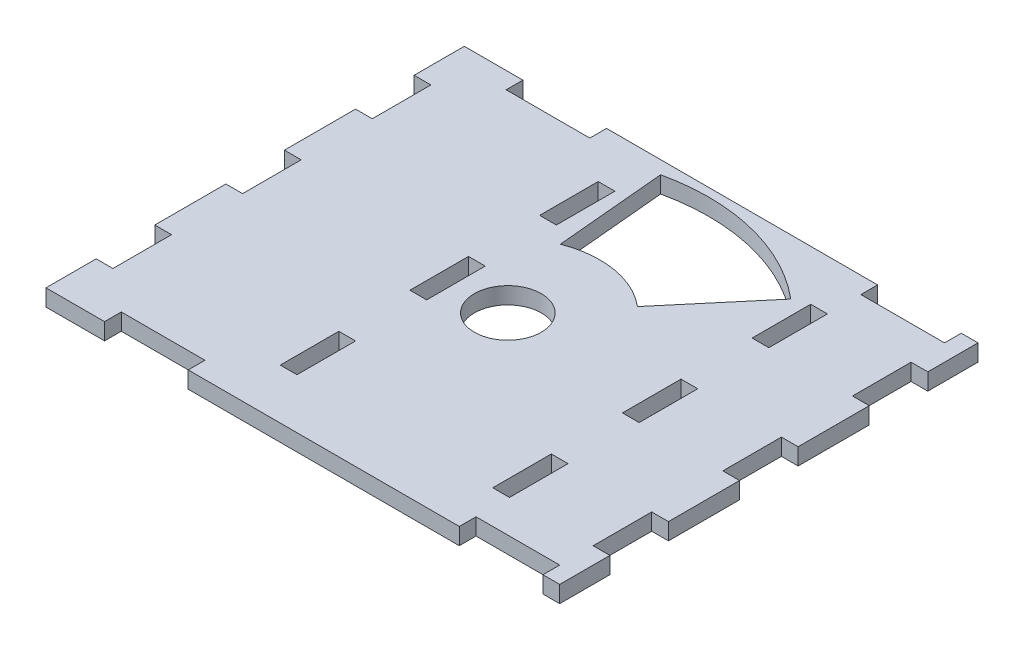
SolidWorks part; units mm, degrees
ref_plane "Front Plane" through (0, 0, 0) normal (0, 0, 1) x (1, 0, 0)
ref_plane "Top Plane" through (0, 0, 0) normal (0, 1, 0) x (1, 0, 0)
ref_plane "Right Plane" through (0, 0, 0) normal (1, 0, 0) x (0, 0, -1)
sketch "Sketch2" plane through (0, 0, 0) normal (0, 1, 0) x (1, 0, 0)
  line L1 (-50, 25) -> (50, 25)
  line L2 (-50, 25) -> (-50, -25)
  line L3 (-50, -25) -> (50, -25)
  line L4 (50, 25) -> (50, -25)
  line L5 (-50, 25) -> (50, -25) construction
  line L6 (-50, -25) -> (50, 25) construction
  circle A0 centre (0, 0) radius 4
  point P0 (0, 0)
  dimension "D3" = 8
  dimension "D1" = 100
  dimension "D2" = 50
extrude "Boss-Extrude1" add sketch "Sketch2" along normal blind 2
sketch "Sketch5" plane through (0, 0, 0) normal (0, -1, 0) x (-1, 0, 0)
  line L0 (-50, 25) -> (50, 25) construction
  line L1 (-17.2, -19) -> (-19.2, -19)
  line L2 (-17.2, -19) -> (-17.2, -12)
  line L3 (-17.2, -12) -> (-19.2, -12)
  line L4 (-19.2, -19) -> (-19.2, -12)
  line L5 (-17.2, -3.5) -> (-19.2, -3.5)
  line L6 (-17.2, -3.5) -> (-17.2, 3.5)
  line L7 (-17.2, 3.5) -> (-19.2, 3.5)
  line L8 (-19.2, -3.5) -> (-19.2, 3.5)
  line L9 (-17.2, 12) -> (-19.2, 12)
  line L10 (-17.2, 12) -> (-17.2, 19)
  line L11 (-17.2, 19) -> (-19.2, 19)
  line L12 (-19.2, 12) -> (-19.2, 19)
  line L13 (8.2, 12) -> (6.2, 12)
  line L14 (8.2, 12) -> (8.2, 19)
  line L15 (8.2, 19) -> (6.2, 19)
  line L16 (6.2, 12) -> (6.2, 19)
  line L17 (8.2, -3.5) -> (6.2, -3.5)
  line L18 (8.2, -3.5) -> (8.2, 3.5)
  line L19 (8.2, 3.5) -> (6.2, 3.5)
  line L20 (6.2, -3.5) -> (6.2, 3.5)
  line L21 (8.2, -19) -> (6.2, -19)
  line L22 (8.2, -19) -> (8.2, -12)
  line L23 (8.2, -12) -> (6.2, -12)
  line L24 (6.2, -19) -> (6.2, -12)
  line L25 (50, -25) -> (-50, -25) construction
  line L26 (-50, 25) -> (50, 25) construction
  line L27 (50, -25) -> (-50, -25) construction
  point P29 (-18.2, -19)
  dimension "D1" = 2
  dimension "D2" = 7
  dimension "D3" = 7
  dimension "D4" = 7
  dimension "D5" = 2
  dimension "D6" = 2
  dimension "D7" = 2
  dimension "D8" = 2
  dimension "D9" = 2
  dimension "D10" = 7
  dimension "D11" = 7
  dimension "D12" = 7
  dimension "D13" = 6
  dimension "D14" = 8.5
  dimension "D15" = 8.5
  dimension "D16" = 6
  dimension "D17" = 6
  dimension "D18" = 8.5
  dimension "D19" = 8.5
  dimension "D20" = 6
  dimension "D21" = 6.2
  dimension "D22" = 0
  dimension "D23" = 17.2
extrude "Cut-Extrude3" cut sketch "Sketch5" against normal blind 2
sketch "Sketch10" plane through (0, 2, 0) normal (0, 1, 0) x (1, 0, 0)
  line L0 (-5.1716, 23.4362) -> (-3.9753, 10.2565)
  line L1 (15.4739, 18.3455) -> (7.0922, 8.4084)
  arc A0 (-3.9753, 10.2565) -> (7.0922, 8.4084) centre (0, 0) cw
  arc A1 (-5.1716, 23.4362) -> (15.4739, 18.3455) centre (0, 0) cw
  point P2 (15.4739, 18.3455)
  dimension "D1" = 24
  dimension "D2" = 11
extrude "Cut-Extrude6" cut sketch "Sketch10" against normal blind 2 contours A1 L0 A0 L1 region at (3.832, 2, -17.0402)
sketch "Sketch11" plane through (0, 2, 0) normal (0, 1, 0) x (1, 0, 0)
  line L0 (-50, -25) -> (50, -25) construction
  line L1 (-18.2, -25) -> (-13.2, -25)
  line L2 (-18.2, -25) -> (-18.2, -23)
  line L3 (-18.2, -23) -> (-13.2, -23)
  line L4 (-13.2, -25) -> (-13.2, -23)
  line L5 (50, 25) -> (-50, 25) construction
  line L6 (29.2, -25) -> (24.2, -25)
  line L7 (29.2, -25) -> (29.2, -23)
  line L8 (29.2, -23) -> (24.2, -23)
  line L9 (24.2, -25) -> (24.2, -23)
  line L10 (29.2, 25) -> (24.2, 25)
  line L11 (29.2, 25) -> (29.2, 23)
  line L12 (29.2, 23) -> (24.2, 23)
  line L13 (24.2, 25) -> (24.2, 23)
  line L15 (-18.2, 25) -> (-13.2, 25)
  line L16 (-18.2, 25) -> (-18.2, 23)
  line L17 (-18.2, 23) -> (-13.2, 23)
  line L18 (-13.2, 25) -> (-13.2, 23)
  dimension "D1" = 2
  dimension "D2" = 2
  dimension "D3" = 2
  dimension "D4" = 2
  dimension "D5" = 5
  dimension "D6" = 5
  dimension "D7" = 5
  dimension "D8" = 5
  dimension "D9" = 5
  dimension "D10" = 5
  dimension "D11" = 5
  dimension "D12" = 5
extrude "Cut-Extrude7" cut sketch "Sketch11" against normal blind 2
sketch "Sketch12" plane through (0, 2, 0) normal (0, 1, 0) x (1, 0, 0)
  line L0 (-50, -25) -> (-18.2, -25) construction
  line L1 (-40.2, -25) -> (-50, -25)
  line L2 (-40.2, -25) -> (-40.2, 25)
  line L3 (-40.2, 25) -> (-50, 25)
  line L4 (-50, -25) -> (-50, 25)
  line L5 (29.2, -25) -> (50, -25) construction
  line L6 (41.2, -25) -> (50, -25)
  line L7 (41.2, -25) -> (41.2, 25)
  line L8 (41.2, 25) -> (50, 25)
  line L9 (50, -25) -> (50, 25)
  line L10 (-18.2, 25) -> (-18.2, 23) construction
  point P16 (-18.2, 24)
  dimension "D1" = 22
  dimension "D2" = 12
extrude "Cut-Extrude8" cut sketch "Sketch12" against normal blind 6
sketch "Sketch13" plane through (0, 2, 0) normal (0, 1, 0) x (1, 0, 0)
  line L1 (-28.2, 19) -> (-30.2, 19)
  line L2 (-28.2, 19) -> (-28.2, 12)
  line L3 (-28.2, 12) -> (-30.2, 12)
  line L4 (-30.2, 19) -> (-30.2, 12)
  line L5 (-28.2, 3.5) -> (-30.2, 3.5)
  line L6 (-28.2, 3.5) -> (-28.2, -3.5)
  line L7 (-28.2, -3.5) -> (-30.2, -3.5)
  line L8 (-30.2, 3.5) -> (-30.2, -3.5)
  line L9 (-28.2, -12) -> (-30.2, -12)
  line L10 (-28.2, -12) -> (-28.2, -19)
  line L11 (-28.2, -19) -> (-30.2, -19)
  line L12 (-30.2, -12) -> (-30.2, -19)
  line L13 (29.2, 19) -> (31.2, 19)
  line L14 (29.2, 19) -> (29.2, 12)
  line L15 (29.2, 12) -> (31.2, 12)
  line L16 (31.2, 19) -> (31.2, 12)
  line L17 (29.2, 3.5) -> (31.2, 3.5)
  line L18 (29.2, 3.5) -> (29.2, -3.5)
  line L19 (29.2, -3.5) -> (31.2, -3.5)
  line L20 (31.2, 3.5) -> (31.2, -3.5)
  line L21 (29.2, -12) -> (31.2, -12)
  line L22 (29.2, -12) -> (29.2, -19)
  line L23 (29.2, -19) -> (31.2, -19)
  line L24 (31.2, -12) -> (31.2, -19)
  line L26 (24.2, 25) -> (-13.2, 25) construction
  line L27 (41.2, 25) -> (29.2, 25) construction
  line L28 (29.2, -25) -> (41.2, -25) construction
  line L29 (-18.2, 25) -> (-40.2, 25) construction
  line L30 (-40.2, -25) -> (-18.2, -25) construction
  line L31 (-40.2, -25) -> (-30.2, -25)
  line L32 (-40.2, -25) -> (-40.2, 25)
  line L33 (-40.2, 25) -> (-30.2, 25)
  line L34 (-30.2, -25) -> (-30.2, 25)
  line L35 (41.2, -25) -> (31.2, -25)
  line L36 (41.2, -25) -> (41.2, 25)
  line L37 (41.2, 25) -> (31.2, 25)
  line L38 (31.2, -25) -> (31.2, 25)
  line L39 (24.2, -25) -> (19.2, -25)
  line L40 (24.2, -25) -> (24.2, -23)
  line L41 (24.2, -23) -> (19.2, -23)
  line L42 (19.2, -25) -> (19.2, -23)
  line L43 (24.2, 23) -> (19.2, 23)
  line L44 (24.2, 23) -> (24.2, 25)
  line L45 (24.2, 25) -> (19.2, 25)
  line L46 (19.2, 23) -> (19.2, 25)
  line L48 (-23.2, 25) -> (-18.2, 25)
  line L49 (-23.2, 25) -> (-23.2, 23)
  line L50 (-23.2, 23) -> (-18.2, 23)
  line L51 (-18.2, 25) -> (-18.2, 23)
  line L52 (-23.2, -25) -> (-18.2, -25)
  line L53 (-23.2, -25) -> (-23.2, -23)
  line L54 (-23.2, -23) -> (-18.2, -23)
  line L55 (-18.2, -25) -> (-18.2, -23)
  point P30 (30.2, 3.5)
  line M32 (41.2, -25) -> (41.2, 25)
  line M33 (41.2, 25) -> (29.2, 25)
  line M36 (24.2, 23) -> (24.2, 25)
  line M37 (24.2, 25) -> (-13.2, 25)
  line M41 (-18.2, 25) -> (-40.2, 25)
  line M42 (-40.2, 25) -> (-40.2, -25)
  line M43 (-40.2, -25) -> (-18.2, -25)
  line M44 (-18.2, -25) -> (-18.2, -23)
  line M51 (29.2, -25) -> (41.2, -25)
  dimension "D1" = 2
  dimension "D2" = 2
  dimension "D3" = 2
  dimension "D4" = 2
  dimension "D5" = 2
  dimension "D6" = 2
  dimension "D7" = 57.4
  dimension "D8" = 57.4
  dimension "D9" = 57.4
  dimension "D10" = 7
  dimension "D11" = 7
  dimension "D12" = 7
  dimension "D13" = 7
  dimension "D14" = 7
  dimension "D15" = 7
  dimension "D16" = 5
  dimension "D17" = 5
  dimension "D18" = 5
  dimension "D19" = 6
  dimension "D20" = 8.5
  dimension "D21" = 8.5
  dimension "D22" = 6
  dimension "D23" = 6
  dimension "D24" = 8.5
  dimension "D25" = 8.5
  dimension "D26" = 6
  dimension "D27" = 5
  dimension "D28" = 2
  dimension "D29" = 2
  dimension "D30" = 2
  dimension "D31" = 2
  dimension "D32" = 5
  dimension "D33" = 5
extrude "Cut-Extrude10" cut sketch "Sketch13" against normal blind 6 contours L9 L12 L11 L10 | L34 L12 L8 L4 M43 M41 M42 | L54 L53 M43 M44 | L24 L21 L22 L23 | L38 L16 L20 L24 M51 M32 M33 | L20 L17 L18 L19 | L46 L43 M36 M37 | L8 L7 L6 L5 | L4 L3 L2 L1 | L48 L51 L50 L49 | L39 L42 L41 L40 | L14 L15 L16 L13 region at (-20.7, 2, 24) region at (-35.2, 2, 0) region at (-29.2, 2, 15.5) region at (36.2, 2, 0) region at (30.2, 2, 0) region at (30.2, 2, 15.5) region at (21.7, 2, -24)
